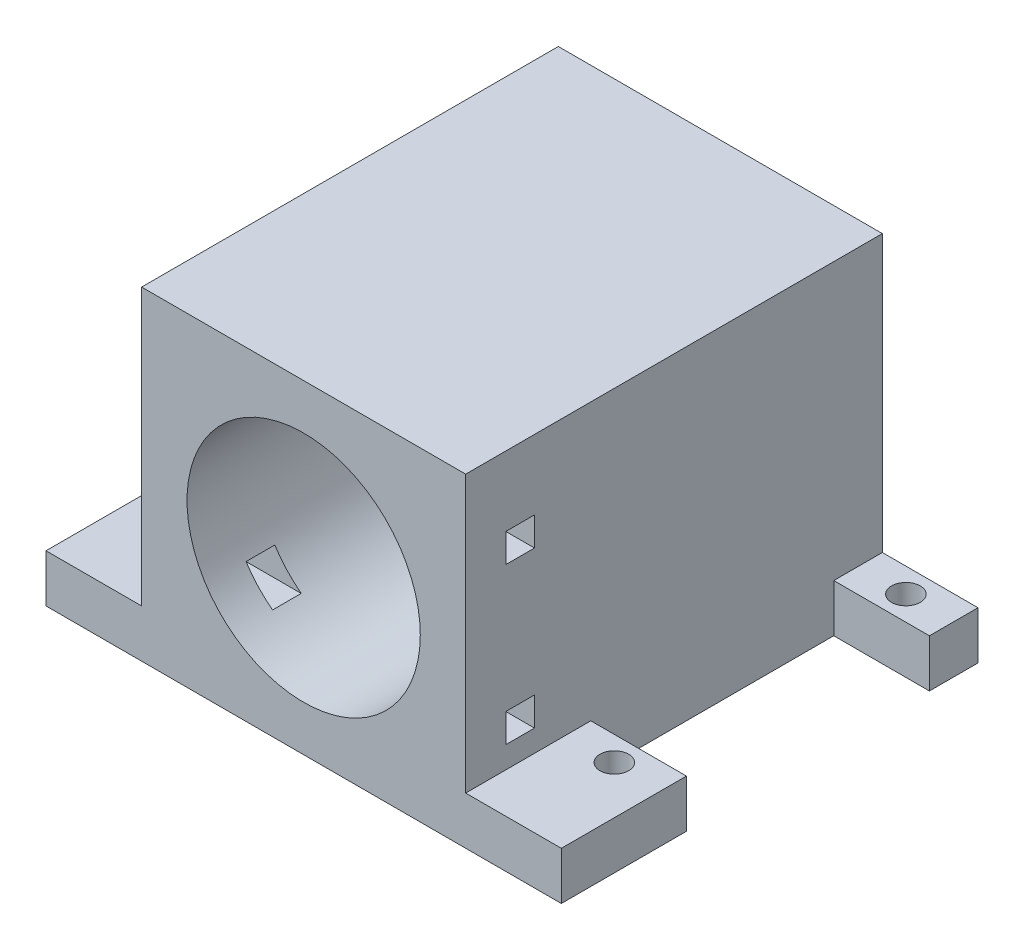
SolidWorks part; units mm, degrees
ref_plane "Front Plane" through (0, 0, 0) normal (0, 0, 1) x (1, 0, 0)
ref_plane "Top Plane" through (0, 0, 0) normal (0, 1, 0) x (1, 0, 0)
ref_plane "Right Plane" through (0, 0, 0) normal (1, 0, 0) x (0, 0, -1)
sketch "Sketch1" plane through (0, 0, 0) normal (0, 0, 1) x (1, 0, 0)
  line L2 (16.938, -11.938) -> (26.938, -11.938)
  line L3 (26.938, -11.938) -> (26.938, -16.938)
  line L4 (26.938, -16.938) -> (-26.938, -16.938)
  line L5 (-26.938, -16.938) -> (-26.938, -11.938)
  line L6 (-26.938, -11.938) -> (-16.938, -11.938)
  line L10 (-16.938, -11.938) -> (-16.938, 16.938)
  line L11 (-16.938, 16.938) -> (16.938, 16.938)
  line L12 (16.938, 16.938) -> (16.938, -12.4887)
  circle A0 centre (0, 0) radius 11.938 construction
  circle A1 centre (0, 0) radius 16.938 construction
  circle A3 centre (0, 0) radius 3.5
  dimension "D1" = 23.876
  dimension "D2" = 5
  dimension "D3" = 7
  dimension "D4" = 10
  dimension "D5" = 5
extrude "Boss-Extrude1" add sketch "Sketch1" along normal mid plane 35.56 contours L12 L11 L10 L6 L5 L4 L3 L2 A3 region at (21.938, -12.5744, 0)
sketch "Sketch2" plane through (0, 0, 0) normal (0, 0, 1) x (1, 0, 0)
  circle A0 centre (0, 0) radius 12.192
  dimension "D1" = 24.384
extrude "Cut-Extrude1" cut sketch "Sketch2" against normal mid plane 30.48
sketch "Sketch4" plane through (0, 0, 17.78) normal (0, 0, 1) x (1, 0, 0)
  line L1 (-11.219, 0) -> (-9.219, 0)
  line L2 (-11.219, 0) -> (-11.219, -2)
  line L3 (-11.219, -2) -> (-9.219, -2)
  line L4 (-9.219, 0) -> (-9.219, -2)
  line L6 (9.219, 0) -> (11.219, 0)
  line L7 (9.219, 0) -> (9.219, -2)
  line L8 (9.219, -2) -> (11.219, -2)
  line L9 (11.219, 0) -> (11.219, -2)
  line L10 (-9.219, 0) -> (9.219, 0) construction
  point P12 (0, 0)
  dimension "D1" = 2
  dimension "D2" = 2
  dimension "D3" = 18.438
extrude "Cut-Extrude3" cut sketch "Sketch4" against normal up to next
sketch "Sketch5" plane through (0, -11.938, 0) normal (0, 1, 0) x (1, 0, 0)
  line L0 (-26.938, -17.78) -> (-26.938, 17.78) construction
  line L1 (-26.938, 12.7) -> (-16.938, 12.7)
  line L2 (-26.938, 12.7) -> (-26.938, -12.7)
  line L3 (-26.938, -12.7) -> (-16.938, -12.7)
  line L4 (-16.938, 12.7) -> (-16.938, -12.7)
  line L7 (16.938, 12.7) -> (26.938, 12.7)
  line L8 (16.938, 12.7) -> (16.938, -12.7)
  line L9 (16.938, -12.7) -> (26.938, -12.7)
  line L10 (26.938, 12.7) -> (26.938, -12.7)
  line L11 (26.938, -17.78) -> (26.938, 17.78) construction
  line L12 (0, -55) -> (0, 55) construction
  line L13 (-55, 0) -> (55, 0) construction
  line L14 (16.938, -17.78) -> (16.938, 17.78) construction
  line L15 (-16.938, -17.78) -> (-16.938, 17.78) construction
  circle A0 centre (-21.938, 15.24) radius 1.5
  circle A1 centre (21.938, 15.24) radius 1.5
  circle A2 centre (21.938, -15.24) radius 1.5
  circle A3 centre (-21.938, -15.24) radius 1.5
  point P16 (-26.938, 0)
  point P17 (26.938, 0)
  point P26 (-21.938, 12.7)
  dimension "D2" = 3
  dimension "D1" = 25.4
  dimension "D3" = 2.54
extrude "Cut-Extrude4" cut sketch "Sketch5" against normal up to next
extrude "Cut-Extrude5" cut sketch "Sketch2<2>" along normal up to next
sketch "Sketch2<2>" plane through (0, 0, 0) normal (0, 0, 1) x (1, 0, 0) same geometry as "Sketch2"
sketch "Sketch6" plane through (0, 0, 17.78) normal (0, 0, 1) x (1, 0, 0)
  line L0 (-16.938, -11.938) -> (-26.938, -11.938)
  line L1 (-26.938, -11.938) -> (-26.938, -16.938)
  line L2 (-26.938, -16.938) -> (26.938, -16.938)
  line L3 (26.938, -16.938) -> (26.938, -11.938)
  line L4 (26.938, -11.938) -> (16.938, -11.938)
  line L5 (16.938, -11.938) -> (16.938, 16.938)
  line L6 (16.938, 16.938) -> (-16.938, 16.938)
  line L7 (-16.938, 16.938) -> (-16.938, -11.938)
  circle A0 centre (0, 0) radius 12.192
extrude "Boss-Extrude2" add sketch "Sketch6" along normal blind 8
sketch "Sketch7" plane through (16.938, 0, 0) normal (1, 0, 0) x (0, 0, -1)
  line L1 (-21.5876, 9.652) -> (-18.5876, 9.652)
  line L2 (-21.5876, 9.652) -> (-21.5876, 6.652)
  line L3 (-21.5876, 6.652) -> (-18.5876, 6.652)
  line L4 (-18.5876, 9.652) -> (-18.5876, 6.652)
  line L5 (-21.5876, -6.652) -> (-18.5876, -6.652)
  line L6 (-21.5876, -6.652) -> (-21.5876, -9.652)
  line L7 (-21.5876, -9.652) -> (-18.5876, -9.652)
  line L8 (-18.5876, -6.652) -> (-18.5876, -9.652)
  line L9 (15.24, 12.192) -> (15.24, -12.192) construction
  dimension "D1" = 2.54
  dimension "D2" = 2.54
  dimension "D3" = 3
  dimension "D4" = 3
  dimension "D5" = 33.8276
  dimension "D6" = 3
extrude "Cut-Extrude6" cut sketch "Sketch7" against normal up to surface (33.876 mm away) up to face at (-16.938, -5.969, 2)
